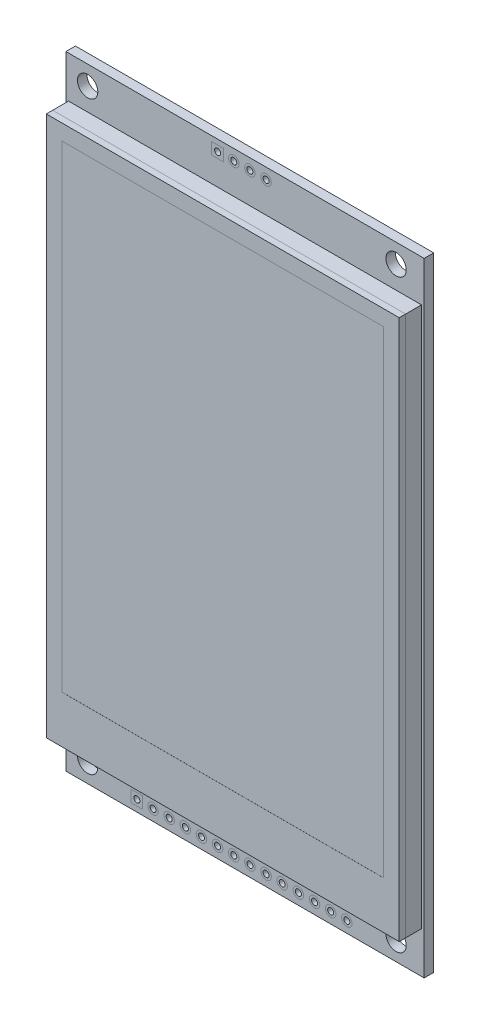
SolidWorks part; units mm, degrees
ref_plane "Спереди" through (0, 0, 0) normal (0, 0, 1) x (1, 0, 0)
ref_plane "Сверху" through (0, 0, 0) normal (0, 1, 0) x (1, 0, 0)
ref_plane "Справа" through (0, 0, 0) normal (1, 0, 0) x (0, 0, -1)
other "Configuration Table"
sketch "Эскиз1" plane through (0, 0, 0) normal (0, 0, 1) x (1, 0, 0)
  line L0 (326.7617, 659.5) -> (1633.4283, 659.5) construction
  line L1 (0, 0) -> (56.34, 0)
  line L2 (0, 0) -> (0, 98)
  line L3 (0, 98) -> (56.34, 98)
  line L4 (56.34, 0) -> (56.34, 98)
  line L5 (3.42, 95) -> (51.92, 95) construction
  line L6 (3.42, 95) -> (3.42, 3) construction
  line L7 (3.42, 3) -> (51.92, 3) construction
  line L8 (51.92, 95) -> (51.92, 3) construction
  line L9 (10.235, 2.665) -> (12.085, 0.815) construction
  line L10 (10.235, 2.665) -> (12.085, 2.665)
  line L11 (10.235, 2.665) -> (10.235, 0.815)
  line L12 (10.235, 0.815) -> (12.085, 0.815)
  line L13 (12.085, 2.665) -> (12.085, 0.815)
  line L14 (11.16, 1.74) -> (13.7, 1.74) construction
  line L15 (13.7, 1.74) -> (16.24, 1.74) construction
  line L16 (16.24, 1.74) -> (18.78, 1.74) construction
  line L17 (18.78, 1.74) -> (21.32, 1.74) construction
  line L18 (21.32, 1.74) -> (23.86, 1.74) construction
  line L19 (23.86, 1.74) -> (26.4, 1.74) construction
  line L20 (26.4, 1.74) -> (28.94, 1.74) construction
  line L21 (28.94, 1.74) -> (31.48, 1.74) construction
  line L22 (31.48, 1.74) -> (34.02, 1.74) construction
  line L23 (34.02, 1.74) -> (36.56, 1.74) construction
  line L24 (36.56, 1.74) -> (39.1, 1.74) construction
  line L25 (39.1, 1.74) -> (41.64, 1.74) construction
  line L26 (41.64, 1.74) -> (44.18, 1.74) construction
  line L27 (24.785, 97.205) -> (22.935, 95.355) construction
  line L28 (22.935, 97.205) -> (24.785, 97.205)
  line L29 (22.935, 97.205) -> (22.935, 95.355)
  line L30 (22.935, 95.355) -> (24.785, 95.355)
  line L31 (24.785, 97.205) -> (24.785, 95.355)
  line L32 (23.86, 96.28) -> (26.4, 96.28) construction
  line L33 (26.4, 96.28) -> (28.94, 96.28) construction
  line L34 (28.94, 96.28) -> (31.48, 96.28) construction
  line L35 (27.67, 95) -> (27.67, 96.28) construction
  line L36 (27.67, 3) -> (27.67, 1.74) construction
  circle A0 centre (3.42, 95) radius 1.6
  circle A1 centre (51.92, 95) radius 1.6
  circle A2 centre (51.92, 3) radius 1.6
  circle A3 centre (3.42, 3) radius 1.6
  circle A4 centre (26.4, 96.28) radius 0.475
  circle A5 centre (26.4, 96.28) radius 0.825
  circle A6 centre (28.94, 96.28) radius 0.475
  circle A7 centre (31.48, 96.28) radius 0.475
  circle A8 centre (31.48, 96.28) radius 0.825
  circle A9 centre (28.94, 96.28) radius 0.825
  circle A10 centre (23.86, 96.28) radius 0.475
  circle A11 centre (11.16, 1.74) radius 0.475
  circle A12 centre (13.7, 1.74) radius 0.475
  circle A13 centre (16.24, 1.74) radius 0.475
  circle A14 centre (18.78, 1.74) radius 0.475
  circle A15 centre (21.32, 1.74) radius 0.475
  circle A16 centre (23.86, 1.74) radius 0.475
  circle A17 centre (26.4, 1.74) radius 0.475
  circle A18 centre (28.94, 1.74) radius 0.475
  circle A19 centre (31.48, 1.74) radius 0.475
  circle A20 centre (34.02, 1.74) radius 0.475
  circle A21 centre (36.56, 1.74) radius 0.475
  circle A22 centre (39.1, 1.74) radius 0.475
  circle A23 centre (41.64, 1.74) radius 0.475
  circle A24 centre (44.18, 1.74) radius 0.475
  circle A25 centre (13.7, 1.74) radius 0.825
  circle A26 centre (16.24, 1.74) radius 0.825
  circle A27 centre (18.78, 1.74) radius 0.825
  circle A28 centre (21.32, 1.74) radius 0.825
  circle A29 centre (23.86, 1.74) radius 0.825
  circle A30 centre (26.4, 1.74) radius 0.825
  circle A31 centre (28.94, 1.74) radius 0.825
  circle A32 centre (31.48, 1.74) radius 0.825
  circle A33 centre (34.02, 1.74) radius 0.825
  circle A34 centre (36.56, 1.74) radius 0.825
  circle A35 centre (39.1, 1.74) radius 0.825
  circle A36 centre (41.64, 1.74) radius 0.825
  circle A37 centre (44.18, 1.74) radius 0.825
  dimension "D3" = 3.2
  dimension "D11" = 0.95
  dimension "D12" = 1.65
  dimension "D14" = 0.95
  dimension "D1" = 56.34
  dimension "D2" = 98
  dimension "D4" = 3
  dimension "D5" = 3
  dimension "D6" = 3.42
  dimension "D7" = 4.42
  dimension "D8" = 1.85
  dimension "D9" = 1.85
  dimension "D10" = 2.54
  dimension "D13" = 1.72
  dimension "D15" = 1.74
  dimension "D16" = 2.54
extrude "Бобышка-Вытянуть1" add sketch "Эскиз1" along normal blind 1.5 contours L1 L4 L3 L2 A37 A36 A35 A34 A33 A32 A31 A30 A29 A28 A27 A26 A25 A9 A8 A5 A3 A2 A1 A0 L10 L13 L12 L11 L28 region at (28.1815, 49.1854, 0)
extrude "Бобышка-Вытянуть2" add sketch "Эскиз1<3>" along normal blind 1.5 separate body contours L13 L10 L11 L12 A11 | A25 A12 | A26 A13 | A27 A14 | A28 A15 | A29 A16 | A30 A17 | A32 A19 | A31 A18 | A34 A21 | A33 A20 | A35 A22 | A36 A23 | A37 A24 | L31 L28 L29 L30 A10 | A5 A4 | A9 A6 | A8 A7 region at (11.16, 2.6388, 0) region at (23.86, 97.1788, 0) region at (25.5983, 96.28, 0) region at (30.6783, 96.28, 0) region at (28.1383, 96.28, 0) region at (12.8983, 1.74, 0) region at (15.4383, 1.74, 0) region at (17.9783, 1.74, 0) region at (20.5183, 1.74, 0) region at (23.0583, 1.74, 0) region at (25.5983, 1.74, 0) region at (28.1383, 1.74, 0) region at (30.6783, 1.74, 0) region at (33.2183, 1.74, 0) region at (35.7583, 1.74, 0) region at (38.2983, 1.74, 0) region at (40.8383, 1.74, 0) region at (43.3783, 1.74, 0)
sketch "Эскиз1<3>" plane through (0, 0, 0) normal (0, 0, 1) x (1, 0, 0) same geometry as "Эскиз1"
sketch "Эскиз2" plane through (0, 0, 1.5) normal (0, 0, 1) x (1, 0, 0)
  line L0 (0, 98) -> (56.34, 98) construction
  line L1 (0.42, 91.46) -> (55.92, 91.46)
  line L2 (0.42, 91.46) -> (0.42, 6.5)
  line L3 (0.42, 6.5) -> (55.92, 6.5)
  line L4 (55.92, 91.46) -> (55.92, 6.5)
  line L5 (0, 0) -> (56.34, 0) construction
  line L6 (28.17, 91.46) -> (28.17, 98) construction
  dimension "D1" = 55.5
  dimension "D2" = 6.54
  dimension "D3" = 6.5
extrude "Бобышка-Вытянуть3" add sketch "Эскиз2" along normal blind 2.5 separate body
sketch "Эскиз3" plane through (0, 0, 4) normal (0, 0, 1) x (1, 0, 0)
  line L1 (0.42, 91.46) -> (55.92, 91.46)
  line L2 (0.42, 91.46) -> (0.42, 6.5)
  line L3 (0.42, 6.5) -> (55.92, 6.5)
  line L4 (55.92, 91.46) -> (55.92, 6.5)
extrude "Бобышка-Вытянуть4" add sketch "Эскиз3" along normal blind 1 separate body
sketch "Эскиз4" plane through (0, 0, 5) normal (0, 0, 1) x (1, 0, 0)
  line L0 (28.17, 89) -> (28.17, 98) construction
  line L1 (2.88, 89) -> (53.46, 89)
  line L2 (2.88, 89) -> (2.88, 13.94)
  line L3 (2.88, 13.94) -> (53.46, 13.94)
  line L4 (53.46, 89) -> (53.46, 13.94)
  line L5 (0, 98) -> (56.34, 98) construction
  line L6 (53.46, 89) -> (55.92, 91.46) construction
  line L7 (55.92, 6.5) -> (55.92, 91.46) construction
  line L8 (55.92, 91.46) -> (0.42, 91.46) construction
  line L10 (0.42, 6.5) -> (55.92, 6.5) construction
  dimension "D1" = 2.46
  dimension "D2" = 75.06
  dimension "D3" = 7.44
  dimension "D4" = 2.46
extrude "Вырез-Вытянуть1" cut sketch "Эскиз4" against normal blind 0.01
sketch "Эскиз6" plane through (0, 0, 4.99) normal (0, 0, 1) x (1, 0, 0)
  line L4 (2.88, 89) -> (3.69, 88.19) construction
  line L5 (2.88, 89) -> (2.88, 13.94) construction
  line L6 (28.17, 89) -> (28.17, 88.19) construction
  line L7 (53.46, 89) -> (2.88, 89) construction
  line L8 (53.46, 13.94) -> (53.46, 89) construction
  line L9 (2.88, 13.94) -> (53.46, 13.94) construction
  line L10 (53.46, 89) -> (2.88, 89) construction
  line L12 (3.69, 88.19) -> (3.69, 14.75)
  line L13 (3.69, 14.75) -> (52.65, 14.75)
  line L14 (52.65, 14.75) -> (52.65, 88.19)
  line L15 (52.65, 88.19) -> (3.69, 88.19)
  dimension "D1" = 45
  dimension "D2" = 48.96
  dimension "D3" = 73.44
  dimension "D4" = 0.81
  dimension "D5" = 0.81
  dimension "D6" = 0.81
sketch "Эскиз7" plane through (0, 0, 4.99) normal (0, 0, 1) x (1, 0, 0)
  line L1 (3.69, 88.19) -> (52.65, 88.19)
  line L2 (3.69, 88.19) -> (3.69, 14.75)
  line L3 (3.69, 14.75) -> (52.65, 14.75)
  line L4 (52.65, 88.19) -> (52.65, 14.75)
sketch "Эскиз8" plane through (0, 0, 0) normal (0, 0, -1) x (-1, 0, 0)
  line L0 (270.4167, 659.5) -> (1577.0833, 659.5) construction
  line L2 (-29.3483, 68.2247) -> (-27.9483, 68.2247)
  line L3 (-29.3483, 68.2247) -> (-29.3483, 67.5247)
  line L4 (-29.3483, 67.5247) -> (-27.9483, 67.5247)
  line L5 (-27.9483, 68.2247) -> (-27.9483, 67.5247)
  line L6 (-29.3483, 65.8187) -> (-27.9483, 65.8187)
  line L7 (-29.3483, 65.8187) -> (-29.3483, 65.1187)
  line L8 (-29.3483, 65.1187) -> (-27.9483, 65.1187)
  line L9 (-27.9483, 65.8187) -> (-27.9483, 65.1187)
  line L10 (-29.3483, 63.4804) -> (-27.9483, 63.4804)
  line L11 (-29.3483, 63.4804) -> (-29.3483, 62.7804)
  line L12 (-29.3483, 62.7804) -> (-27.9483, 62.7804)
  line L13 (-27.9483, 63.4804) -> (-27.9483, 62.7804)
  line L14 (-43.0288, 23.4277) -> (-41.6288, 23.4277)
  line L15 (-43.0288, 23.4277) -> (-43.0288, 22.7277)
  line L16 (-43.0288, 22.7277) -> (-41.6288, 22.7277)
  line L17 (-41.6288, 23.4277) -> (-41.6288, 22.7277)
  line L18 (-43.0522, 16.2217) -> (-41.6522, 16.2217)
  line L19 (-43.0522, 16.2217) -> (-43.0522, 15.5217)
  line L20 (-43.0522, 15.5217) -> (-41.6522, 15.5217)
  line L21 (-41.6522, 16.2217) -> (-41.6522, 15.5217)
  line L22 (-37.0217, 17.8928) -> (-35.6217, 17.8928)
  line L23 (-37.0217, 17.8928) -> (-37.0217, 17.1928)
  line L24 (-37.0217, 17.1928) -> (-35.6217, 17.1928)
  line L25 (-35.6217, 17.8928) -> (-35.6217, 17.1928)
  line L26 (-37.0217, 16.2456) -> (-35.6217, 16.2456)
  line L27 (-37.0217, 16.2456) -> (-37.0217, 15.5456)
  line L28 (-37.0217, 15.5456) -> (-35.6217, 15.5456)
  line L29 (-35.6217, 16.2456) -> (-35.6217, 15.5456)
  line L30 (-23.7699, 21.6472) -> (-22.3699, 21.6472)
  line L31 (-23.7699, 21.6472) -> (-23.7699, 20.9472)
  line L32 (-23.7699, 20.9472) -> (-22.3699, 20.9472)
  line L33 (-22.3699, 21.6472) -> (-22.3699, 20.9472)
  line L34 (-23.6158, 19.0191) -> (-22.6158, 19.0191)
  line L35 (-23.6158, 19.0191) -> (-23.6158, 16.4191)
  line L36 (-23.6158, 16.4191) -> (-22.6158, 16.4191)
  line L37 (-22.6158, 19.0191) -> (-22.6158, 16.4191)
  line L38 (-43.6639, 19.7712) -> (-41.0639, 19.7712)
  line L39 (-43.6639, 19.7712) -> (-43.6639, 18.7712)
  line L40 (-43.6639, 18.7712) -> (-41.0639, 18.7712)
  line L41 (-41.0639, 19.7712) -> (-41.0639, 18.7712)
  line L42 (-33.5538, 22.0725) -> (-28.5195, 22.0725)
  line L43 (-33.5538, 22.0725) -> (-33.5538, 17.9344)
  line L44 (-33.5538, 17.9344) -> (-28.5195, 17.9344)
  line L45 (-28.5195, 22.0725) -> (-28.5195, 17.9344)
  dimension "D1" = 1.4
  dimension "D2" = 0.7
  dimension "D3" = 1.4
  dimension "D4" = 0.7
  dimension "D5" = 0.7
  dimension "D6" = 1.4
  dimension "D7" = 1.4
  dimension "D8" = 0.7
  dimension "D9" = 0.7
  dimension "D10" = 1.4
  dimension "D11" = 1
  dimension "D12" = 2.6
  dimension "D13" = 2.6
  dimension "D14" = 1
  dimension "D15" = 1.4
  dimension "D16" = 0.7
extrude "Бобышка-Вытянуть5" add sketch "Эскиз8" along normal blind 0.8 separate body
sketch "Эскиз9" plane through (0, 0, 0) normal (0, 0, -1) x (-1, 0, 0)
  line L0 (-43.6639, 19.7712) -> (-41.0639, 19.7712) construction
  line L1 (-23.6158, 19.0191) -> (-23.6158, 16.4191) construction
  line L2 (-33.2538, 22.0725) -> (-32.6203, 22.0725) construction
  line L3 (-33.5538, 22.0725) -> (-28.5195, 22.0725) construction
  line L4 (-32.6203, 22.0725) -> (-31.9868, 22.0725) construction
  line L5 (-31.9868, 22.0725) -> (-31.3533, 22.0725) construction
  line L6 (-31.3533, 22.0725) -> (-30.7199, 22.0725) construction
  line L7 (-30.7199, 22.0725) -> (-30.0864, 22.0725) construction
  line L8 (-30.0864, 22.0725) -> (-29.4529, 22.0725) construction
  line L9 (-29.4529, 22.0725) -> (-28.8195, 22.0725) construction
  line L10 (-33.5538, 22.0725) -> (-33.5538, 17.9344) construction
  line L11 (-28.5195, 22.0725) -> (-28.5195, 17.9344) construction
  line L12 (-33.5538, 20.0034) -> (-28.5195, 20.0034) construction
  line L13 (-29.4529, 17.9344) -> (-28.8195, 17.9344) construction
  line L14 (-33.3788, 22.7225) -> (-33.1288, 22.7225)
  line L15 (-33.3788, 22.7225) -> (-33.3788, 22.0725)
  line L16 (-33.3788, 22.0725) -> (-33.1288, 22.0725)
  line L17 (-33.1288, 22.7225) -> (-33.1288, 22.0725)
  line L18 (-32.7453, 22.7225) -> (-32.4953, 22.7225)
  line L19 (-32.7453, 22.7225) -> (-32.7453, 22.0725)
  line L20 (-32.7453, 22.0725) -> (-32.4953, 22.0725)
  line L21 (-32.4953, 22.7225) -> (-32.4953, 22.0725)
  line L22 (-32.1118, 22.7225) -> (-31.8618, 22.7225)
  line L23 (-32.1118, 22.7225) -> (-32.1118, 22.0725)
  line L24 (-32.1118, 22.0725) -> (-31.8618, 22.0725)
  line L25 (-31.8618, 22.7225) -> (-31.8618, 22.0725)
  line L26 (-31.4783, 22.7225) -> (-31.2283, 22.7225)
  line L27 (-31.4783, 22.7225) -> (-31.4783, 22.0725)
  line L28 (-31.4783, 22.0725) -> (-31.2283, 22.0725)
  line L29 (-31.2283, 22.7225) -> (-31.2283, 22.0725)
  line L30 (-30.8449, 22.7225) -> (-30.5949, 22.7225)
  line L31 (-30.8449, 22.7225) -> (-30.8449, 22.0725)
  line L32 (-30.8449, 22.0725) -> (-30.5949, 22.0725)
  line L33 (-30.5949, 22.7225) -> (-30.5949, 22.0725)
  line L34 (-30.2114, 22.7225) -> (-29.9614, 22.7225)
  line L35 (-30.2114, 22.7225) -> (-30.2114, 22.0725)
  line L36 (-30.2114, 22.0725) -> (-29.9614, 22.0725)
  line L37 (-29.9614, 22.7225) -> (-29.9614, 22.0725)
  line L38 (-29.5779, 22.7225) -> (-29.3279, 22.7225)
  line L39 (-29.5779, 22.7225) -> (-29.5779, 22.0725)
  line L40 (-29.5779, 22.0725) -> (-29.3279, 22.0725)
  line L41 (-29.3279, 22.7225) -> (-29.3279, 22.0725)
  line L42 (-28.9445, 22.7225) -> (-28.6945, 22.7225)
  line L43 (-28.9445, 22.7225) -> (-28.9445, 22.0725)
  line L44 (-28.9445, 22.0725) -> (-28.6945, 22.0725)
  line L45 (-28.6945, 22.7225) -> (-28.6945, 22.0725)
  line L46 (-30.0864, 17.9344) -> (-29.4529, 17.9344) construction
  line L47 (-30.7199, 17.9344) -> (-30.0864, 17.9344) construction
  line L48 (-31.3533, 17.9344) -> (-30.7199, 17.9344) construction
  line L49 (-31.9868, 17.9344) -> (-31.3533, 17.9344) construction
  line L50 (-32.6203, 17.9344) -> (-31.9868, 17.9344) construction
  line L51 (-33.2538, 17.9344) -> (-32.6203, 17.9344) construction
  line L52 (-28.6945, 17.2844) -> (-28.6945, 17.9344)
  line L53 (-28.9445, 17.9344) -> (-28.6945, 17.9344)
  line L54 (-28.9445, 17.2844) -> (-28.9445, 17.9344)
  line L55 (-28.9445, 17.2844) -> (-28.6945, 17.2844)
  line L56 (-29.3279, 17.2844) -> (-29.3279, 17.9344)
  line L57 (-29.5779, 17.9344) -> (-29.3279, 17.9344)
  line L58 (-29.5779, 17.2844) -> (-29.5779, 17.9344)
  line L59 (-29.5779, 17.2844) -> (-29.3279, 17.2844)
  line L60 (-29.9614, 17.2844) -> (-29.9614, 17.9344)
  line L61 (-30.2114, 17.9344) -> (-29.9614, 17.9344)
  line L62 (-30.2114, 17.2844) -> (-30.2114, 17.9344)
  line L63 (-30.2114, 17.2844) -> (-29.9614, 17.2844)
  line L64 (-30.5949, 17.2844) -> (-30.5949, 17.9344)
  line L65 (-30.8449, 17.9344) -> (-30.5949, 17.9344)
  line L66 (-30.8449, 17.2844) -> (-30.8449, 17.9344)
  line L67 (-30.8449, 17.2844) -> (-30.5949, 17.2844)
  line L68 (-31.2283, 17.2844) -> (-31.2283, 17.9344)
  line L69 (-31.4783, 17.9344) -> (-31.2283, 17.9344)
  line L70 (-31.4783, 17.2844) -> (-31.4783, 17.9344)
  line L71 (-31.4783, 17.2844) -> (-31.2283, 17.2844)
  line L72 (-31.8618, 17.2844) -> (-31.8618, 17.9344)
  line L73 (-32.1118, 17.9344) -> (-31.8618, 17.9344)
  line L74 (-32.1118, 17.2844) -> (-32.1118, 17.9344)
  line L75 (-32.1118, 17.2844) -> (-31.8618, 17.2844)
  line L76 (-32.4953, 17.2844) -> (-32.4953, 17.9344)
  line L77 (-32.7453, 17.9344) -> (-32.4953, 17.9344)
  line L78 (-32.7453, 17.2844) -> (-32.7453, 17.9344)
  line L79 (-32.7453, 17.2844) -> (-32.4953, 17.2844)
  line L80 (-33.1288, 17.2844) -> (-33.1288, 17.9344)
  line L81 (-33.3788, 17.9344) -> (-33.1288, 17.9344)
  line L82 (-33.3788, 17.2844) -> (-33.3788, 17.9344)
  line L83 (-33.3788, 17.2844) -> (-33.1288, 17.2844)
  line L84 (-22.6158, 19.0191) -> (-22.6158, 16.4191) construction
  line L85 (-42.5639, 20.7712) -> (-42.1639, 20.7712)
  line L86 (-42.5639, 20.7712) -> (-42.5639, 19.7712)
  line L87 (-42.5639, 19.7712) -> (-42.1639, 19.7712)
  line L88 (-42.1639, 20.7712) -> (-42.1639, 19.7712)
  line L89 (-43.5139, 18.7712) -> (-43.1139, 18.7712)
  line L90 (-43.5139, 18.7712) -> (-43.5139, 17.7712)
  line L91 (-43.5139, 17.7712) -> (-43.1139, 17.7712)
  line L92 (-43.1139, 18.7712) -> (-43.1139, 17.7712)
  line L93 (-41.6139, 18.7712) -> (-41.2139, 18.7712)
  line L94 (-41.6139, 18.7712) -> (-41.6139, 17.7712)
  line L95 (-41.6139, 17.7712) -> (-41.2139, 17.7712)
  line L96 (-41.2139, 18.7712) -> (-41.2139, 17.7712)
  line L97 (-24.6158, 17.9191) -> (-23.6158, 17.9191)
  line L98 (-24.6158, 17.9191) -> (-24.6158, 17.5191)
  line L99 (-24.6158, 17.5191) -> (-23.6158, 17.5191)
  line L100 (-23.6158, 17.9191) -> (-23.6158, 17.5191)
  line L101 (-22.6158, 16.9691) -> (-21.6158, 16.9691)
  line L102 (-22.6158, 16.9691) -> (-22.6158, 16.5691)
  line L103 (-22.6158, 16.5691) -> (-21.6158, 16.5691)
  line L104 (-21.6158, 16.9691) -> (-21.6158, 16.5691)
  line L105 (-22.6158, 18.8691) -> (-21.6158, 18.8691)
  line L106 (-22.6158, 18.8691) -> (-22.6158, 18.4691)
  line L107 (-22.6158, 18.4691) -> (-21.6158, 18.4691)
  line L108 (-21.6158, 18.8691) -> (-21.6158, 18.4691)
  line L109 (-23.6158, 19.0191) -> (-22.6158, 19.0191) construction
  line L110 (-23.6158, 16.4191) -> (-22.6158, 16.4191) construction
  line L111 (-41.0639, 19.7712) -> (-41.0639, 18.7712) construction
  line L112 (-43.6639, 19.7712) -> (-43.6639, 18.7712) construction
  line L113 (-43.6639, 18.7712) -> (-41.0639, 18.7712) construction
  point P0 (-42.3639, 19.7712)
  point P1 (-23.6158, 17.7191)
  dimension "D1" = 0.3
  dimension "D2" = 0.3
  dimension "D3" = 0.65
  dimension "D4" = 0.25
  dimension "D5" = 0.4
  dimension "D6" = 1
  dimension "D7" = 0.15
  dimension "D8" = 0.15
  dimension "D9" = 0.15
  dimension "D10" = 0.15
  dimension "D11" = 0.4
  dimension "D12" = 1
extrude "Бобышка-Вытянуть6" add sketch "Эскиз9" along normal blind 0.35 separate body
